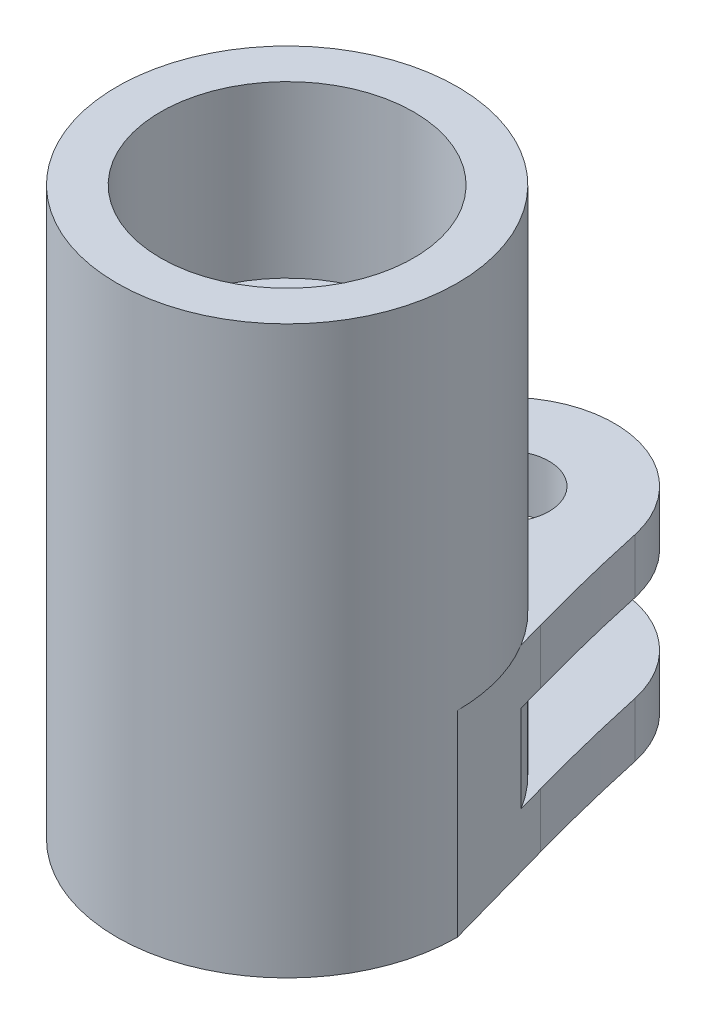
SolidWorks part; units mm, degrees
material "PLA"
ref_plane "Alzado" through (0, 0, 0) normal (0, 0, 1) x (1, 0, 0)
ref_plane "Planta" through (0, 0, 0) normal (0, 1, 0) x (1, 0, 0)
ref_plane "Vista lateral" through (0, 0, 0) normal (1, 0, 0) x (0, 0, -1)
sketch "Croquis1" plane through (0, 0, 0) normal (0, 1, 0) x (1, 0, 0)
  line L0 (0, 0) -> (0, 5) construction
  line L1 (-3.9, 0) -> (-2.5, 5)
  line L2 (2.5, 5) -> (3.9, 0)
  arc A1 (-3.9, 0) -> (3.9, 0) centre (0, 0) ccw
  arc A2 (2.5, 5) -> (-2.5, 5) centre (0, 5) ccw
  dimension "D1" = 5
  dimension "D2" = 5
  dimension "D3" = 3.9
extrude "Saliente-Extruir1" add sketch "Croquis1" along normal blind 4.5
sketch "Croquis3" plane through (0, 4.5, 0) normal (0, 1, 0) x (1, 0, 0)
  circle A0 centre (0, 0) radius 2.9
  circle A1 centre (0, 5) radius 1
  dimension "D1" = 2
  dimension "D2" = 5.8
extrude "Cortar-Extruir1" cut sketch "Croquis3" against normal through all
sketch "Croquis4" plane through (0, 4.5, 0) normal (0, 1, 0) x (1, 0, 0)
  circle A0 centre (0, 0) radius 3.9
  circle A1 centre (0, 0) radius 2.9
  dimension "D1" = 5.8
  dimension "D2" = 7.8
extrude "Saliente-Extruir2" add sketch "Croquis4" along normal blind 5
sketch "Croquis5" plane through (0, 4.5, 0) normal (0, 1, 0) x (1, 0, 0)
  line L6 (3.3329, 2.0252) -> (2.5, 5) construction
  line L7 (-2.5, 5) -> (-3.3329, 2.0252) construction
  line L8 (3.3329, 2.0252) -> (2.5, 5)
  line L9 (-2.5, 5) -> (-3.3329, 2.0252)
  arc A1 (3.3329, 2.0252) -> (-3.3329, 2.0252) centre (0, 0) ccw construction
  arc A2 (2.5, 5) -> (-2.5, 5) centre (0, 5) ccw construction
  arc A3 (3.3329, 2.0252) -> (-3.3329, 2.0252) centre (0, 0) ccw
  arc A4 (2.5, 5) -> (-2.5, 5) centre (0, 5) ccw
sketch "Croquis6" plane through (0, 9.5, 0) normal (0, 1, 0) x (1, 0, 0)
  circle A0 centre (0, 0) radius 2.9 construction
  circle A1 centre (0, 0) radius 3.9
  circle A2 centre (0, 0) radius 3.9
  circle A3 centre (0, 0) radius 2.9
  dimension "D1" = 0
extrude "Saliente-Extruir3" add sketch "Croquis6" along normal blind 3.48
extrude "Cortar-Extruir3" cut sketch "Croquis5" against normal mid plane 2 from offset 2.25 offset against normal yes
sketch "Croquis7" plane through (0, 0, 0) normal (0, -1, 0) x (1, 0, 0)
  circle A0 centre (0, 0) radius 2.9
  circle A1 centre (0, 0) radius 1.5
  dimension "D1" = 5.8
  dimension "D2" = 3
extrude "Saliente-Extruir4" add sketch "Croquis7" along normal blind 1 from offset 9.08 offset against normal yes
fillet "Redondeo1" radius 50 4 edges at (2.5, 3.875, -5) (2.5, 0.625, -5) (-2.5, 0.625, -5) (-2.5, 3.875, -5)
